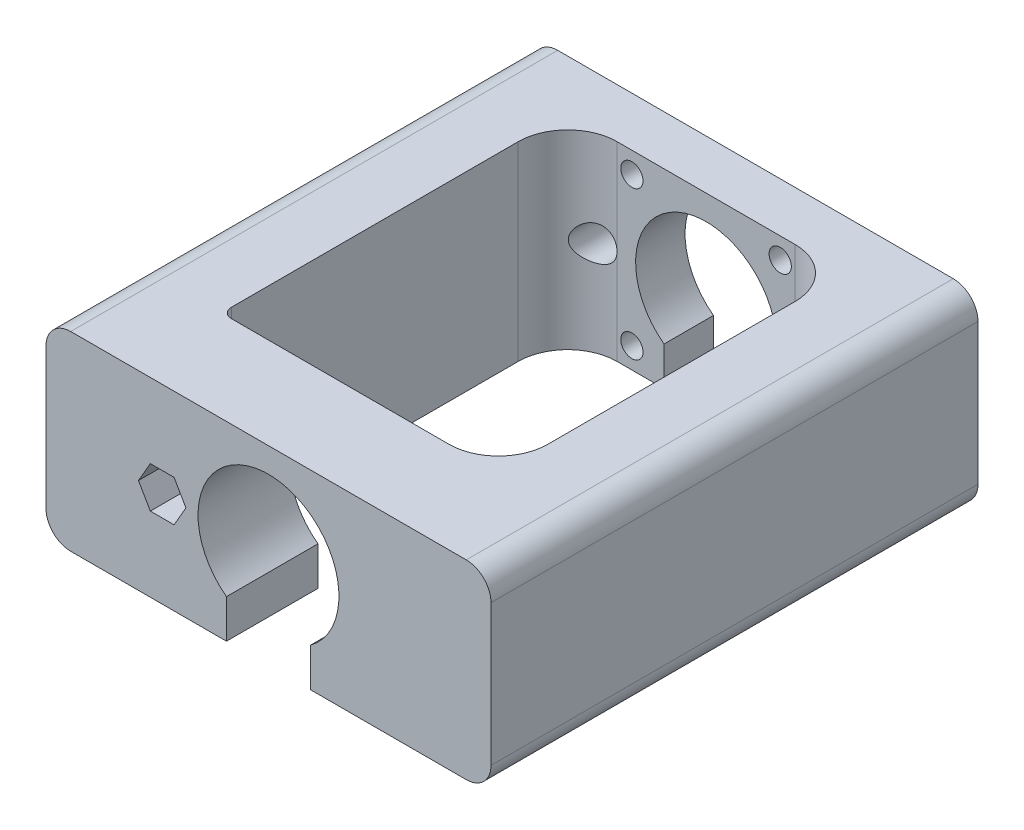
SolidWorks part; units mm, degrees
ref_plane "Front Plane" through (0, 0, 0) normal (0, 0, 1) x (1, 0, 0)
ref_plane "Top Plane" through (0, 0, 0) normal (0, 1, 0) x (1, 0, 0)
ref_plane "Right Plane" through (0, 0, 0) normal (1, 0, 0) x (0, 0, -1)
sketch "Sketch1" plane through (0, 0, 0) normal (0, 0, 1) x (1, 0, 0)
  line L0 (-15, 19.25) -> (-30, 19.25)
  line L2 (-45, 14.25) -> (-45, -14.25)
  line L4 (-15, 19.25) -> (15, 19.25)
  line L6 (15, -19.25) -> (8.5, -19.25)
  line L11 (-30, -19.25) -> (-15, -19.25)
  line L12 (-30, 19.25) -> (-40, 19.25)
  line L13 (-30, -19.25) -> (-40, -19.25)
  line L14 (-8.5, -19.25) -> (-15, -19.25)
  line L15 (0, 0) -> (0, 9.3162)
  line L16 (30, -19.25) -> (15, -19.25)
  line L17 (8.5, -16.75) -> (8.5, -11.4373)
  line L18 (-8.5, -16.75) -> (-8.5, -11.4373)
  line L19 (-8.5, -16.75) -> (-8.5, -19.25)
  line L20 (8.5, -16.75) -> (8.5, -19.25)
  line L21 (15, 19.25) -> (30, 19.25)
  line L22 (30, -19.25) -> (40, -19.25)
  line L23 (30, 19.25) -> (40, 19.25)
  line L24 (45, 14.25) -> (45, -14.25)
  arc A0 (8.5, -11.4373) -> (-8.5, -11.4373) centre (0, 0) ccw
  circle A1 centre (15, 15) radius 2.25
  circle A2 centre (-15, 15) radius 2.25
  circle A3 centre (-15, -15) radius 2.25
  circle A4 centre (15, -15) radius 2.25
  arc A19 (-40, -19.25) -> (-45, -14.25) centre (-40, -14.25) cw
  arc A20 (-40, 19.25) -> (-45, 14.25) centre (-40, 14.25) ccw
  arc A21 (40, 19.25) -> (45, 14.25) centre (40, 14.25) cw
  arc A22 (40, -19.25) -> (45, -14.25) centre (40, -14.25) ccw
  point P5 (19.25, 15)
  point P7 (-10.75, 15)
  point P13 (-10.75, -15)
  point P18 (-25.25, 0)
  point P19 (19.25, -15)
  point P20 (-15, 15)
  point P22 (15, 15)
  point P24 (15, -15)
  point P26 (-15, -15)
  point P38 (-39.75, 0)
  point P39 (-20.75, 0)
  point P51 (39.75, 0)
  dimension "D1" = 2
  dimension "D3" = 5
  dimension "D2" = 2
extrude "Boss-Extrude1" add sketch "Sketch1" along normal blind 10 contours A19 L11 L6 L4 A4 A3 A2 A1 A0 region at (0, 18.2711, 0)
sketch "Sketch2" plane through (0, 0, 10) normal (0, 0, 1) x (1, 0, 0)
  line L12 (-45, 14.25) -> (-45, -14.25)
  line L14 (-40, 19.25) -> (-28, 19.25)
  line L15 (-28, 0) -> (-28, 19.25)
  line L16 (-28, 0) -> (-28, -19.25)
  line L17 (-40, -19.25) -> (-28, -19.25)
  line L19 (40, -19.25) -> (28, -19.25)
  line L20 (28, 0) -> (28, -19.25)
  line L21 (28, 0) -> (28, 19.25)
  line L22 (40, 19.25) -> (28, 19.25)
  line L23 (45, 14.25) -> (45, -14.25)
  arc A0 (40, 19.25) -> (45, 14.25) centre (40, 14.25) cw
  arc A16 (-45, -14.25) -> (-40, -19.25) centre (-40, -14.25) ccw
  arc A17 (-40, 19.25) -> (-45, 14.25) centre (-40, 14.25) ccw
  arc A18 (45, -14.25) -> (40, -19.25) centre (40, -14.25) cw
extrude "Boss-Extrude3" add sketch "Sketch2" along normal blind 70 separate body
sketch "Sketch4" plane through (0, 0, 80) normal (0, 0, 1) x (1, 0, 0)
  line L5 (-28, -19.25) -> (-28, 19.25)
  line L7 (-45, 14.25) -> (-45, -14.25)
  line L11 (-45, 14.25) -> (-45, -14.25)
  line L21 (-40, 19.25) -> (40, 19.25)
  line L22 (-40, -19.25) -> (-8.5, -19.25)
  line L23 (-40, -19.25) -> (-28, -19.25)
  line L25 (-28, 19.25) -> (-40, 19.25)
  line L27 (-8.5, -11.4373) -> (-8.5, -19.25) construction
  line L28 (8.5, -19.25) -> (8.5, -11.4373) construction
  line L29 (40, 19.25) -> (28, 19.25)
  line L30 (28, 19.25) -> (28, -19.25)
  line L31 (28, -19.25) -> (40, -19.25)
  line L32 (45, -14.25) -> (45, 14.25)
  line L36 (45, -14.25) -> (45, 14.25)
  line L37 (-8.5, -11.4373) -> (-8.5, -19.25)
  line L38 (8.5, -19.25) -> (8.5, -11.4373)
  line L39 (8.5, -19.25) -> (40, -19.25)
  circle A1 centre (-21.5, 0) radius 3.5
  arc A2 (-45, -14.25) -> (-40, -19.25) centre (-40, -14.25) ccw
  arc A3 (-40, 19.25) -> (-45, 14.25) centre (-40, 14.25) ccw
  arc A4 (-45, -14.25) -> (-40, -19.25) centre (-40, -14.25) ccw
  arc A5 (-40, 19.25) -> (-45, 14.25) centre (-40, 14.25) ccw
  arc A11 (8.5, -11.4373) -> (-8.5, -11.4373) centre (0, 0) ccw construction
  arc A12 (45, 14.25) -> (40, 19.25) centre (40, 14.25) ccw
  arc A13 (40, -19.25) -> (45, -14.25) centre (40, -14.25) ccw
  arc A14 (45, 14.25) -> (40, 19.25) centre (40, 14.25) ccw
  arc A15 (40, -19.25) -> (45, -14.25) centre (40, -14.25) ccw
  arc A17 (8.5, -11.4373) -> (-8.5, -11.4373) centre (0, 0) ccw
  dimension "D3" = 0
  dimension "D1" = 0
extrude "Boss-Extrude4" add sketch "Sketch4" along normal blind 10
sketch "Sketch6" plane through (0, 0, 90) normal (0, 0, 1) x (1, 0, 0)
  line L6 (-40, -19.25) -> (-8.5, -19.25)
  line L8 (-40, -19.25) -> (-8.5, -19.25)
  line L9 (45, -14.25) -> (45, 14.25)
  line L10 (-45, 14.25) -> (-45, -14.25)
  line L11 (45, -14.25) -> (45, 14.25)
  line L16 (-45, 14.25) -> (-45, -14.25)
  line L21 (-16.7, 0) -> (-19.1, 4.1569)
  line L22 (-19.1, 4.1569) -> (-23.9, 4.1569)
  line L23 (-23.9, 4.1569) -> (-26.3, 0)
  line L24 (40, 19.25) -> (-40, 19.25)
  line L25 (40, 19.25) -> (-40, 19.25)
  line L26 (-26.3, 0) -> (-23.9, -4.1569)
  line L27 (-23.9, -4.1569) -> (-19.1, -4.1569)
  line L28 (-19.1, -4.1569) -> (-16.7, 0)
  line L30 (8.5, -11.4373) -> (8.5, -19.25)
  line L31 (8.5, -11.4373) -> (8.5, -19.25)
  line L32 (8.5, -19.25) -> (40, -19.25)
  line L33 (8.5, -19.25) -> (40, -19.25)
  line L34 (-8.5, -19.25) -> (-8.5, -11.4373)
  line L35 (-8.5, -19.25) -> (-8.5, -11.4373)
  circle A0 centre (-21.5, 0) radius 4.8 construction
  arc A5 (40, -19.25) -> (45, -14.25) centre (40, -14.25) ccw
  arc A6 (40, -19.25) -> (45, -14.25) centre (40, -14.25) ccw
  arc A9 (45, 14.25) -> (40, 19.25) centre (40, 14.25) ccw
  arc A10 (-40, 19.25) -> (-45, 14.25) centre (-40, 14.25) ccw
  arc A11 (-45, -14.25) -> (-40, -19.25) centre (-40, -14.25) ccw
  arc A16 (-40, 19.25) -> (-45, 14.25) centre (-40, 14.25) ccw
  arc A17 (-45, -14.25) -> (-40, -19.25) centre (-40, -14.25) ccw
  arc A18 (45, 14.25) -> (40, 19.25) centre (40, 14.25) ccw
  arc A20 (8.5, -11.4373) -> (-8.5, -11.4373) centre (0, 0) ccw
  arc A21 (8.5, -11.4373) -> (-8.5, -11.4373) centre (0, 0) ccw
  dimension "D1" = 0
extrude "Boss-Extrude5" add sketch "Sketch6" along normal blind 8.5
sketch "Sketch5" plane through (0, 0, 90) normal (0, 0, 1) x (1, 0, 0)
  circle A0 centre (-21.5, 0) radius 3.5
extrude "Cut-Extrude1" cut sketch "Sketch5" against normal through all
combine bodies "Combine1" operation type add bodies to combine 110 111 113
fillet "Fillet2" radius 2 1 edges at (-28, 0, 80)
fillet "Fillet3" radius 10 3 edges at (-28, 0, 10) (28, 0, 80) (28, 0, 10)
